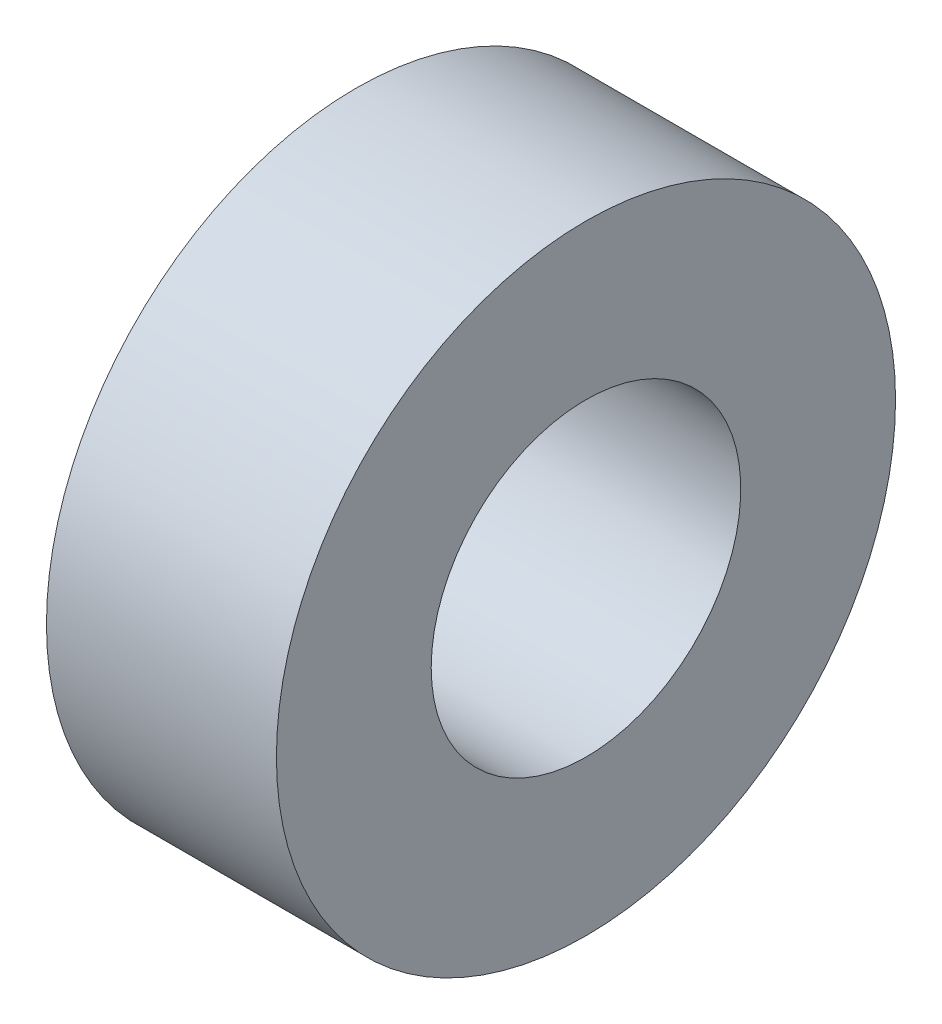
SolidWorks part; units mm, degrees
material "ABS"
ref_plane "정면" through (0, 0, 0) normal (0, 0, 1) x (1, 0, 0)
ref_plane "윗면" through (0, 0, 0) normal (0, 1, 0) x (1, 0, 0)
ref_plane "우측면" through (0, 0, 0) normal (1, 0, 0) x (0, 0, -1)
sketch "Sketch15" plane through (0, 0, 0) normal (0, 0, 1) x (1, 0, 0)
  line L1 (851, 1496) -> (877, 1496)
  line L2 (851, 1496) -> (851, 1461)
  line L3 (851, 1461) -> (877, 1461)
  line L4 (877, 1496) -> (877, 1461)
  point P4 (0, 0)
  point P5 (0, 0)
  dimension "D1" = 1461
  dimension "D2" = 851
  dimension "D3" = 35
  dimension "D4" = 26
revolve "Revolve1" add sketch "Sketch15" angle 360 about L3
sketch "Sketch16" plane through (0, 0, 0) normal (0, 0, 1) x (1, 0, 0)
  line L0 (851, 1496) -> (851, 1461) construction
  line L1 (877, 1461) -> (851, 1461)
  line L2 (877, 1461) -> (877, 1478.5)
  line L3 (877, 1478.5) -> (851, 1478.5)
  line L4 (851, 1461) -> (851, 1478.5)
  dimension "D1" = 17.5
revolve "Cut-Revolve1" cut sketch "Sketch16" angle 360 about L3
scale "Scale1" bodies to scale 127 scale about origin uniform scaling yes scale factor 0.1
equation "\"Mass\"= \"SW-질량\" / 1000"
